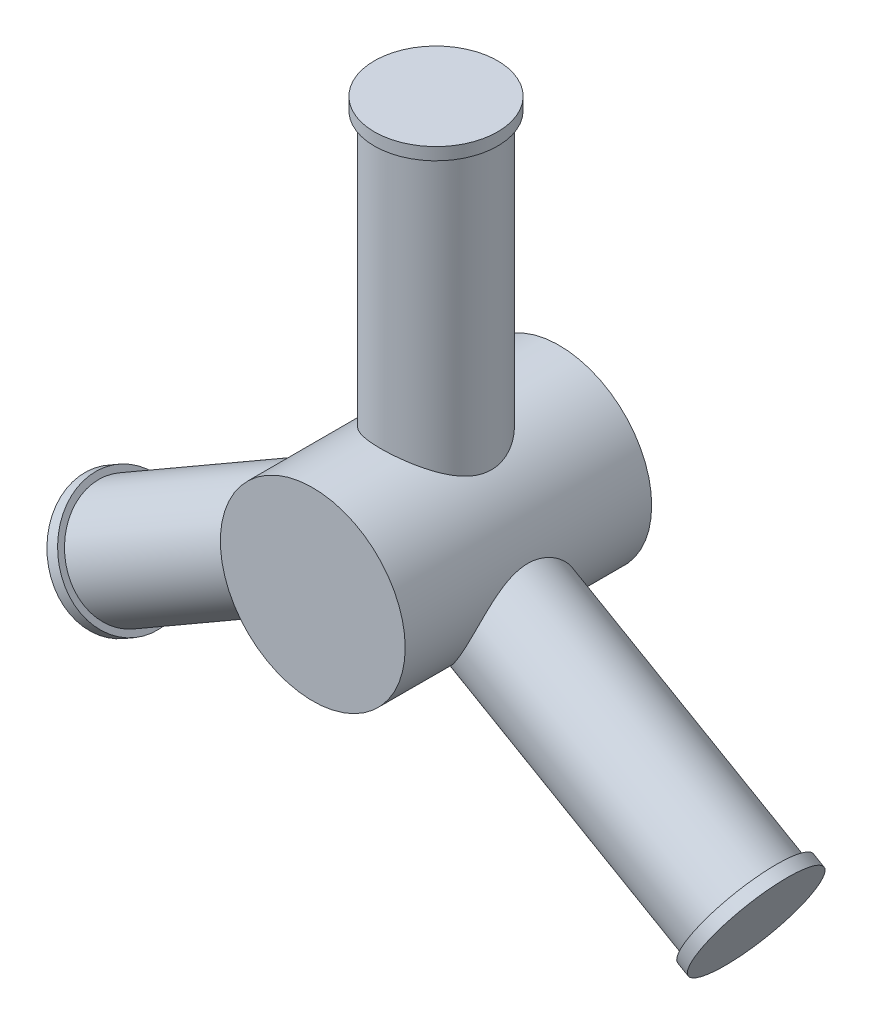
SolidWorks part; units mm, degrees
ref_plane "Ebene vorne" through (0, 0, 0) normal (0, 0, 1) x (1, 0, 0)
ref_plane "Ebene oben" through (0, 0, 0) normal (0, 1, 0) x (1, 0, 0)
ref_plane "Ebene rechts" through (0, 0, 0) normal (1, 0, 0) x (0, 0, -1)
sketch "Skizze1" plane through (0, 0, 0) normal (0, 0, 1) x (1, 0, 0)
  circle A0 centre (0, 0) radius 750
extrude "Aufsatz-Linear austragen1" add sketch "Skizze1" along normal blind 1000 and the other way blind 1000
sketch "Skizze2" plane through (0, 0, 0) normal (0, 1, 0) x (1, 0, 0)
  circle A0 centre (0, 0) radius 450
extrude "Aufsatz-Linear austragen2" add sketch "Skizze2" along normal blind 3000
sketch "Skizze3" plane through (0, 0, 0) normal (0, 1, 0) x (1, 0, 0)
  circle A0 centre (0, 0) radius 500
extrude "Aufsatz-Linear austragen3" add sketch "Skizze3" along normal blind 100 from offset 2900
pattern_circular "Kreismuster1" count 3 over 360 about axis through (0, 0, -1000) along (0, 0, -1) of "Aufsatz-Linear austragen2" reverse direction yes
pattern_circular "Kreismuster2" count 3 over 360 about axis through (0, 0, -1000) along (0, 0, -1) of "Aufsatz-Linear austragen3" reverse direction yes
